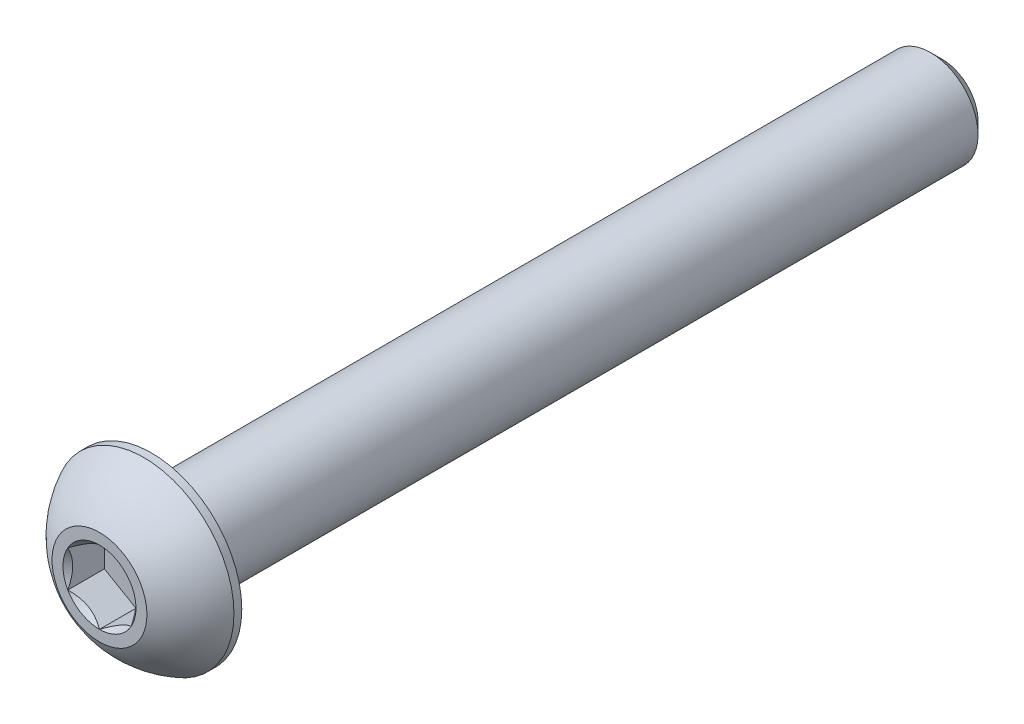
SolidWorks part; units mm, degrees
ref_plane "Front" through (0, 0, 0) normal (0, 0, 1) x (1, 0, 0)
ref_plane "Top" through (0, 0, 0) normal (0, 1, 0) x (1, 0, 0)
ref_plane "Right" through (0, 0, 0) normal (1, 0, 0) x (0, 0, -1)
sketch "Sketch1" plane through (0, 0, 0) normal (1, 0, 0) x (0, 0, -1)
  line L2 (1.65, 1.5) -> (26.65, 1.5)
  line L3 (26.65, 1.5) -> (26.65, 0)
  line L4 (26.65, 0) -> (1.65, 0)
  line L6 (1.4025, 2.85) -> (1.65, 2.85) construction
  line L7 (26.65, 1.5) -> (26.65, -1.5) construction
  line L8 (0, 0) -> (1.65, 0) construction
  line L9 (1.65, 2.85) -> (1.65, -2.85) construction
  line L11 (1.65, 1.5) -> (1.65, 0)
  line L13 (0, 1) -> (0, -1) construction
  line L14 (0, 1) -> (0, 1.5) construction
  arc A3 (0, 1.5) -> (1.4025, 2.85) centre (2.7948, 0) cw construction
  dimension "D1" = 0.2475
revolve "Revolve1" add sketch "Sketch1" angle 360 mid plane about L4
sketch "Sketch3" plane through (0, 0, -26.65) normal (0, 0, -1) x (-1, 0, 0)
  circle A0 centre (0, 0) radius 1.5
curve "Helix/Spiral1" pitch 0.5 height 25.5 turns 51
sketch "Sketch2" plane through (0, 0, 0) normal (1, 0, 0) x (0, 0, -1)
  line L0 (26.65, 1.5) -> (27.0875, 1.5)
  line L1 (27.0875, 1.5) -> (26.9, 1.1752)
  line L2 (26.9, 1.1752) -> (26.8375, 1.1752)
  line L3 (26.8375, 1.1752) -> (26.65, 1.5)
  line L4 (26.7438, 1.3376) -> (26.9938, 1.3376) construction
  dimension "D1" = 60
  dimension "D2" = 0.0625
  dimension "D3" = 0.25
chamfer "Chamfer1" distance 0.375 angle 45 1 edges at (0, 1.5, -26.65)
sweep "Cut-Sweep1" [suppressed] cut profiles "Sketch2" path "Helix/Spiral1"
sketch "Sketch7" plane through (0, 0, 0) normal (1, 0, 0) x (0, 0, -1)
  line L6 (1.4025, 2.85) -> (1.65, 2.85) construction
  line L8 (0, 0) -> (1.65, 0) construction
  line L11 (1.65, 2.85) -> (1.65, -2.85) construction
  line L12 (1.4025, 2.85) -> (1.65, 2.85)
  line L13 (0, 0) -> (1.65, 0)
  line L14 (0, 1) -> (0, -1) construction
  line L15 (1.65, 2.85) -> (1.65, 0)
  line L16 (0, 1.5) -> (0, 0)
  arc A2 (1.4025, 2.85) -> (0, 1.5) centre (2.7948, 0) ccw construction
  arc A3 (1.4025, 2.85) -> (0, 1.5) centre (2.7948, 0) ccw
revolve "Revolve2" add sketch "Sketch7" angle 360 mid plane about L13
sketch "Sketch5" plane through (0, 0, 0) normal (0, 0, 1) x (1, 0, 0)
  line L1 (1, -0.5774) -> (1, 0.5774)
  line L2 (1, 0.5774) -> (0, 1.1547)
  line L3 (0, 1.1547) -> (-1, 0.5774)
  line L4 (-1, 0.5774) -> (-1, -0.5774)
  line L5 (-1, -0.5774) -> (0, -1.1547)
  line L6 (0, -1.1547) -> (1, -0.5774)
  circle A0 centre (0, 0) radius 1 construction
extrude "Cut-Extrude2" cut sketch "Sketch5" against normal blind 1.155
sketch "Sketch6" plane through (0, 0, 0) normal (0, 0, 1) x (1, 0, 0)
  circle A0 centre (0, 0) radius 1.1547
extrude "Cut-Extrude3" cut sketch "Sketch6" against normal blind 1.155 draft 45
sketch "Sketch9" [suppressed] plane through (0, 0, -4.2164) normal (0, 0, 1) x (1, 0, 0)
  circle A2 centre (0, 0) radius 3.9687
extrude "Boss-Extrude2" [suppressed] add sketch "Sketch9" against normal offset from surface (9.525 mm away) 28.575
sketch "Sketch10" plane through (0, 0, 0) normal (1, 0, 0) x (0, 0, -1)
  line L0 (26.65, 1.5) -> (26.65, -1.5) construction
  point P0 (25.9, -1.5)
  dimension "D1" = 0.75
equation "\"D3@Helix/Spiral1\" = \"Lg@Sketch1\" + \"D4@Helix/Spiral1\""
equation "\"D2@Sketch2\" = \"D4@Helix/Spiral1\" * .125"
equation "\"D3@Sketch2\" = \"D4@Helix/Spiral1\" * .5"
equation "\"D1@Chamfer1\" = \"D4@Helix/Spiral1\" * .75"
equation "\"D1@Cut-Extrude2\" = \"Head Ht@Sketch1\" * .7"
equation "\"D1@Sketch1\" = \"Head Ht@Sketch1\" * .15"
equation "\"D1@Sketch10\" = \"D4@Helix/Spiral1\" * 1.5"
equation "\"D1@Cut-Extrude3\" = \"D1@Cut-Extrude2\""
